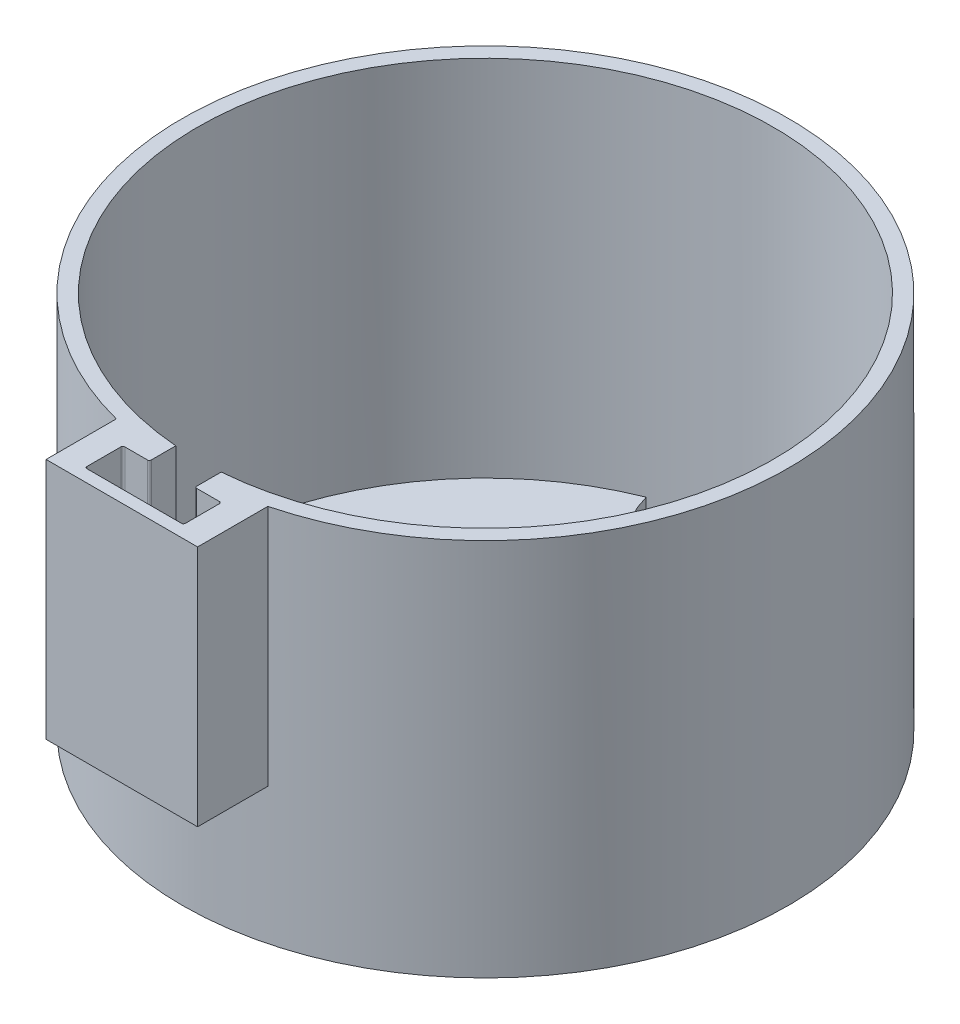
SolidWorks part; units mm, degrees
ref_plane "Front Plane" through (0, 0, 0) normal (0, 0, 1) x (1, 0, 0)
ref_plane "Top Plane" through (0, 0, 0) normal (0, 1, 0) x (1, 0, 0)
ref_plane "Right Plane" through (0, 0, 0) normal (1, 0, 0) x (0, 0, -1)
sketch "Sketch1" plane through (0, 0, 0) normal (0, 1, 0) x (1, 0, 0)
  circle A0 centre (0, 0) radius 40
extrude "Boss-Extrude1" add sketch "Sketch1" along normal blind 40 contours A0
sketch "Sketch2" plane through (0, 40, 0) normal (0, 1, 0) x (1, 0, 0)
  circle A0 centre (0, 0) radius 38
extrude "Cut-Extrude1" cut sketch "Sketch2" against normal blind 38
sketch "Sketch3" plane through (0, 2, 0) normal (0, 1, 0) x (1, 0, 0)
  arc A0 (-14.0761, 35.2968) -> (14.0761, 35.2968) centre (0, 39.1212) ccw
  circle A1 centre (0, 0) radius 38 construction
  circle A2 centre (0, 0) radius 38 construction
  arc A3 (-14.0761, 35.2968) -> (14.0761, 35.2968) centre (0, 0) cw
extrude "Cut-Extrude2" cut sketch "Sketch3" against normal blind 38
sketch "Sketch4" plane through (0, 2, 0) normal (0, 1, 0) x (1, 0, 0)
  circle A0 centre (0, 0) radius 5
extrude "Cut-Extrude3" cut sketch "Sketch4" against normal blind 38
sketch "Sketch6" plane through (0, 0, 0) normal (0, -1, 0) x (1, 0, 0)
  circle A1 centre (-20, 0) radius 2
  circle A2 centre (20, 0) radius 2
extrude "Boss-Extrude2" add sketch "Sketch6" along normal blind 2
sketch "Sketch8" plane through (0, 40, 0) normal (0, 1, 0) x (1, 0, 0)
  circle A0 centre (0, 0) radius 43.4969
sketch "Sketch9" plane through (0, 40, 0) normal (0, 1, 0) x (1, 0, 0)
  circle A3 centre (0, 0) radius 40
  circle A4 centre (0, 0) radius 40
  circle A6 centre (0, 0) radius 38 construction
  circle A7 centre (0, 0) radius 38
  dimension "D1" = 0
extrude "Boss-Extrude3" add sketch "Sketch9" along normal blind 10
sketch "Sketch10" plane through (0, 50, 0) normal (0, 1, 0) x (1, 0, 0)
  line L0 (0, 0) -> (0, -38) construction
  line L4 (0, -38) -> (10, -38)
  line L6 (10, -38) -> (10, -48)
  line L8 (0, -38) -> (-10, -38)
  line L9 (-10, -38) -> (-10, -48)
  line L10 (-10, -48) -> (10, -48)
  circle A0 centre (0, 0) radius 38 construction
extrude "Boss-Extrude4" add sketch "Sketch10" against normal blind 32 contours L8 L9 L10 L6 L4
sketch "Sketch11" plane through (0, 50, 0) normal (0, 1, 0) x (1, 0, 0)
  line L0 (0, -48) -> (0, -38) construction
  line L1 (-10, -48) -> (10, -48) construction
  line L2 (-10, -43.3649) -> (10, -43.3649) construction
  line L3 (-10, -38.7298) -> (-10, -48) construction
  line L4 (10, -38.7298) -> (10, -48) construction
  line L8 (-3, -36.8649) -> (3, -36.8649)
  line L10 (-3, -36.8649) -> (-3, -41.3649)
  line L11 (3, -36.8649) -> (3, -41.3649)
  line L12 (3, -41.3649) -> (6.5, -41.3649)
  line L13 (6.5, -41.3649) -> (6.5, -46.3649)
  line L14 (-3, -41.3649) -> (-6.5, -41.3649)
  line L15 (-6.5, -41.3649) -> (-6.5, -46.3649)
  line L16 (-6.5, -46.3649) -> (6.5, -46.3649)
  arc A0 (-14.0761, 35.2968) -> (14.0761, 35.2968) centre (0, 0) ccw construction
  dimension "D1" = 13
  dimension "D2" = 5
  dimension "D3" = 4.5
  dimension "D4" = 6
extrude "Cut-Extrude4" cut sketch "Sketch11" against normal blind 30
fillet "Fillet1" radius 0.25 6 edges at (-3, 35, 41.3649) (3, 35, 41.3649) (6.5, 35, 41.3649) (-6.5, 35, 41.3649) (6.5, 35, 46.3649) (-6.5, 35, 46.3649)
sketch "Sketch13" plane through (0, 0, 0) normal (0, -1, 0) x (1, 0, 0)
  circle A0 centre (-30, 0) radius 3
  circle A1 centre (30, 0) radius 3
extrude "Cut-Extrude5" cut sketch "Sketch13" against normal blind 10
